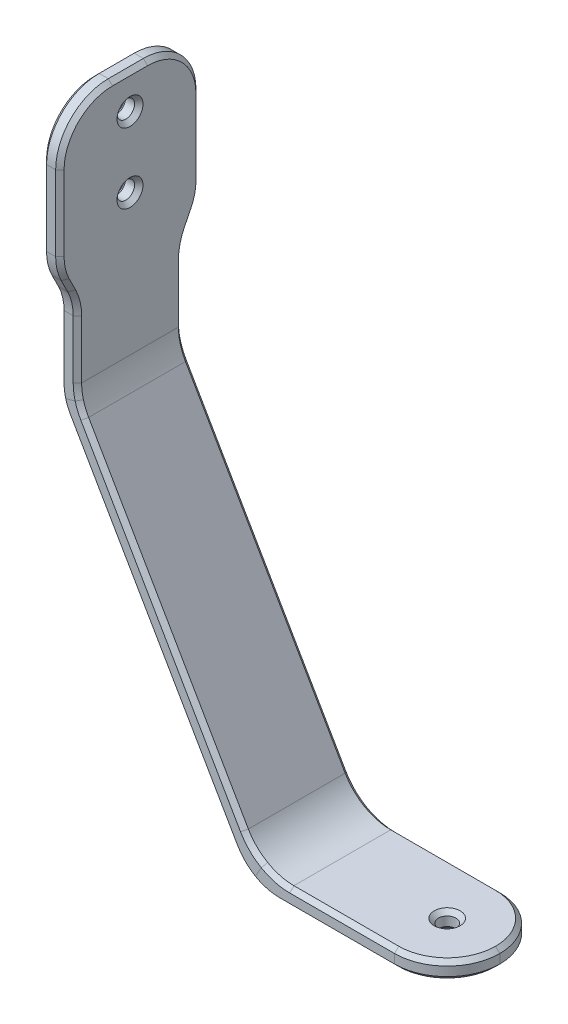
SolidWorks part; units mm, degrees
ref_plane "Front Plane" through (0, 0, 0) normal (0, 0, 1) x (1, 0, 0)
ref_plane "Top Plane" through (0, 0, 0) normal (0, 1, 0) x (1, 0, 0)
ref_plane "Right Plane" through (0, 0, 0) normal (1, 0, 0) x (0, 0, -1)
sketch "Sketch1" plane through (0, 0, 0) normal (0, 0, 1) x (1, 0, 0)
  line L0 (0, 0) -> (0, -47.5145)
  line L1 (0, -47.5145) -> (33.6108, -105.7302)
  line L2 (33.6108, -105.7302) -> (68.5358, -105.7302)
  dimension "D1" = 47.5145
  dimension "D3" = 150
  dimension "D4" = 120
  dimension "D5" = 34.925
  dimension "D2" = 58.2157
sketch "Sketch2" plane through (0, 0, 0) normal (0, 1, 0) x (1, 0, 0)
  line L1 (-1.5875, -9.525) -> (1.5875, -9.525)
  line L2 (-1.5875, -9.525) -> (-1.5875, 9.525)
  line L3 (-1.5875, 9.525) -> (1.5875, 9.525)
  line L4 (1.5875, -9.525) -> (1.5875, 9.525)
  line L5 (-1.5875, -9.525) -> (1.5875, 9.525) construction
  line L6 (-1.5875, 9.525) -> (1.5875, -9.525) construction
  point P0 (0, 0)
  dimension "D1" = 3.175
  dimension "D2" = 19.05
sweep "Sweep1" add profiles "Sketch2" path "Sketch1"
sketch "Sketch7" plane through (0, 0, 0) normal (1, 0, 0) x (0, 0, -1)
  line L0 (-12.7, -25.4) -> (-9.525, -31.75)
  line L1 (-12.7, 0) -> (12.7, 0)
  line L2 (-12.7, 0) -> (-12.7, -25.4)
  line L3 (-12.7, -25.4) -> (12.7, -25.4) construction
  line L4 (12.7, 0) -> (12.7, -25.4)
  line L5 (-9.525, 0) -> (-9.525, -47.0892) construction
  line L6 (-9.525, -31.75) -> (9.525, -31.75)
  line L7 (9.525, 0) -> (9.525, -47.0892) construction
  line L8 (9.525, -31.75) -> (12.7, -25.4)
  dimension "D1" = 25.4
  dimension "D2" = 25.4
  dimension "D3" = 6.35
extrude "Boss-Extrude1" add sketch "Sketch7" along normal mid plane 3.175 contours L2 L0 L6 L8 L4 L1
sketch "Sketch8" plane through (0, 0, 0) normal (1, 0, 0) x (0, 0, -1)
  line L0 (0, -19.05) -> (0, -6.35) construction
  line L1 (0, -6.35) -> (0, 0) construction
  circle A0 centre (0, -6.35) radius 1.5875
  circle A1 centre (0, -19.05) radius 1.5875
  dimension "D1" = 3.175
  dimension "D2" = 6.35
  dimension "D3" = 12.7
extrude "Cut-Extrude1" cut sketch "Sketch8" against normal through all both and the other way through all
sketch "Sketch9" plane through (0, -104.1427, 0) normal (0, 1, 0) x (1, 0, 0)
  line L0 (68.5358, 0) -> (59.0108, 0) construction
  line L1 (68.5358, -9.525) -> (68.5358, 9.525) construction
  circle A0 centre (59.0108, 0) radius 1.5875
  dimension "D1" = 3.175
  dimension "D2" = 9.525
extrude "Cut-Extrude2" cut sketch "Sketch9" against normal through all both and the other way through all
fillet "Fillet1" radius 9.525 12 edges at (0, -31.75, -9.525) (0, -25.4, -12.7) (0, -31.75, 9.525) (0, -25.4, 12.7) (0, 0, -12.7) (0, 0, 12.7) (68.5358, -105.7302, -9.525) (68.5358, -105.7302, 9.525) (1.5875, -47.0892, 0) (-1.5875, -47.9399, 0) (32.6943, -107.3177, 0) (34.5274, -104.1427, 0)
chamfer "Chamfer1" distance 0.762 angle 45 60 edges at (60.5983, -104.1427, 0) (57.4233, -107.3177, 0) (65.746, -107.3177, 6.7352) (65.746, -107.3177, -6.7352) (48.6022, -107.3177, 9.525) (48.6022, -107.3177, -9.525) (35.7283, -106.9931, 9.525) (35.7283, -106.9931, -9.525) (31.4584, -104.5279, 9.525) (31.4584, -104.5279, -9.525) (14.8166, -76.3527, 9.525) (14.8166, -76.3527, -9.525) (-0.8625, -49.0327, 9.525) (-0.8625, -49.0327, -9.525) (-1.506, -46.631, 9.525) (-1.506, -46.631, -9.525) (-1.5875, -39.6931, 9.525) (-1.5875, -31.8102, 9.7798) (-1.5875, -28.575, 11.1125) (-1.5875, -25.3398, 12.4452) (-1.5875, -16.3382, 12.7) (-1.5875, -2.7898, 9.9102) (-1.5875, 0, 0) (-1.5875, -2.7898, -9.9102) (-1.5875, -16.3382, -12.7) (-1.5875, -25.3398, -12.4452) (-1.5875, -28.575, -11.1125) (-1.5875, -31.8102, -9.7798) (-1.5875, -39.6931, -9.525) (-1.5875, -19.05, -1.5875) (-1.5875, -6.35, -1.5875) (65.746, -104.1427, -6.7352) (65.746, -104.1427, 6.7352) (49.5187, -104.1427, -9.525) (49.5187, -104.1427, 9.525) (37.5614, -103.8181, -9.525) (37.5614, -103.8181, 9.525) (33.2914, -101.3529, -9.525) (33.2914, -101.3529, 9.525) (17.3207, -74.3398, -9.525) (17.3207, -74.3398, 9.525) (2.3125, -48.182, -9.525) (2.3125, -48.182, 9.525) (1.669, -45.7802, -9.525) (1.669, -45.7802, 9.525) (1.5875, -39.2677, -9.525) (1.5875, -31.8102, -9.7798) (1.5875, -28.575, -11.1125) (1.5875, -25.3398, -12.4452) (1.5875, -16.3382, -12.7) (1.5875, -2.7898, -9.9102) (1.5875, 0, 0) (1.5875, -2.7898, 9.9102) (1.5875, -16.3382, 12.7) (1.5875, -25.3398, 12.4452) (1.5875, -28.575, 11.1125) (1.5875, -31.8102, 9.7798) (1.5875, -39.2677, 9.525) (1.5875, -20.6375, 0) (1.5875, -7.9375, 0)
equation "\"D2@Sketch1\"=2.59807621 - 0.3069935 + 0.0008725"
equation "\"D1@Sketch1\"=1.25+0.1875+0.433151"
